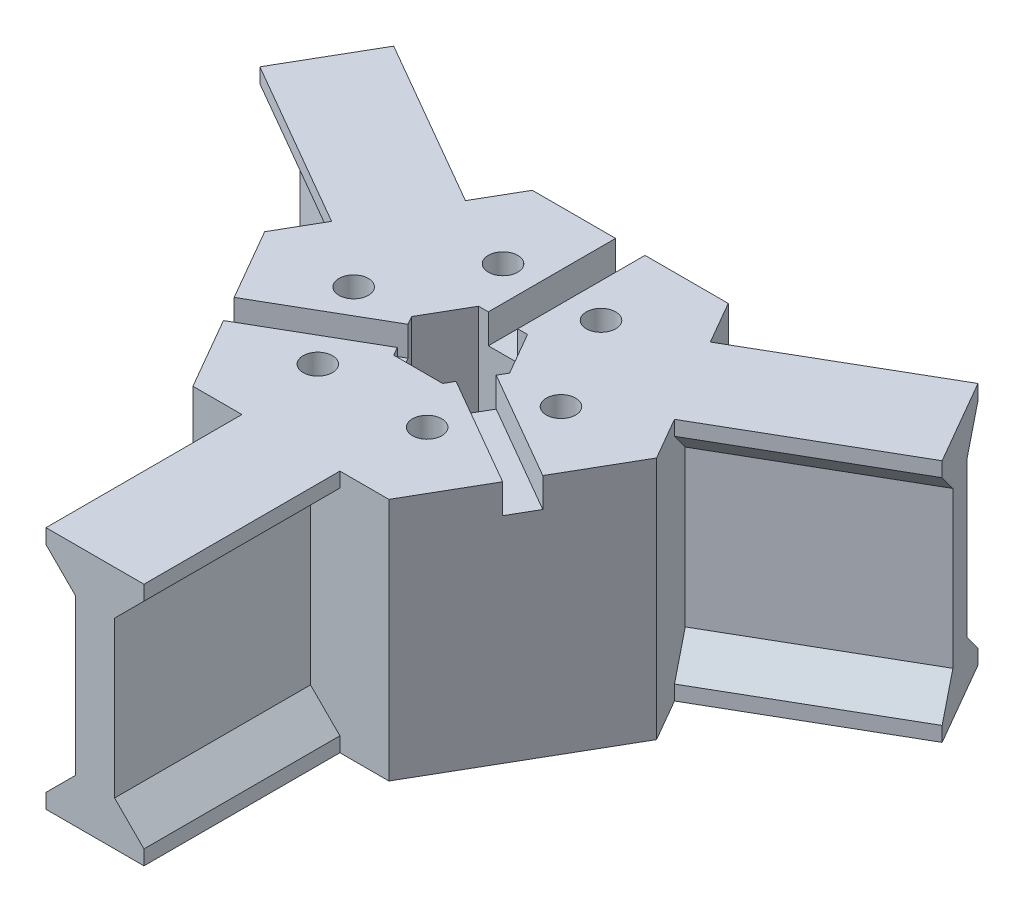
SolidWorks part; units mm, degrees
ref_plane "Front Plane" through (0, 0, 0) normal (0, 0, 1) x (1, 0, 0)
ref_plane "Top Plane" through (0, 0, 0) normal (0, 1, 0) x (1, 0, 0)
ref_plane "Right Plane" through (0, 0, 0) normal (1, 0, 0) x (0, 0, -1)
sketch "Sketch1" plane through (0, 0, 0) normal (0, 1, 0) x (1, 0, 0)
  line L0 (0, -27.9904) -> (0, -34.641) construction
  line L1 (20, 34.641) -> (-20, 34.641)
  line L2 (-20, 34.641) -> (-40, 0)
  line L3 (-40, 0) -> (-20, -34.641)
  line L4 (-20, -34.641) -> (20, -34.641)
  line L5 (20, -34.641) -> (40, 0)
  line L6 (40, 0) -> (20, 34.641)
  line L7 (5, 8.6603) -> (-5, 8.6603)
  line L8 (-5, 8.6603) -> (-10, 0)
  line L9 (-10, 0) -> (-5, -8.6603)
  line L10 (-5, -8.6603) -> (5, -8.6603)
  line L11 (5, -8.6603) -> (10, 0)
  line L12 (10, 0) -> (5, 8.6603)
  line L13 (-11.1603, -37.9904) -> (11.1603, -37.9904) construction
  line L14 (-11.1603, -37.9904) -> (-11.1603, -17.9904) construction
  line L16 (11.1603, -37.9904) -> (11.1603, -17.9904) construction
  line L17 (-11.1603, -37.9904) -> (11.1603, -17.9904) construction
  line L18 (-11.1603, -17.9904) -> (11.1603, -37.9904) construction
  line L19 (-5, -8.6603) -> (5, 8.6603) construction
  line L20 (-25.2452, 14.5753) -> (-30, 17.3205) construction
  line L21 (-21.1603, -0.6699) -> (-40.4904, 10.4904) construction
  line L23 (-10, 18.6603) -> (-29.3301, 29.8205) construction
  line L24 (-40.4904, 10.4904) -> (-29.3301, 29.8205) construction
  line L25 (-21.1603, -0.6699) -> (-29.3301, 29.8205) construction
  line L26 (-10, 18.6603) -> (-40.4904, 10.4904) construction
  line L27 (25.2452, 14.5753) -> (30, 17.3205) construction
  line L28 (21.1603, -0.6699) -> (40.4904, 10.4904) construction
  line L30 (10, 18.6603) -> (29.3301, 29.8205) construction
  line L31 (40.4904, 10.4904) -> (29.3301, 29.8205) construction
  line L32 (21.1603, -0.6699) -> (29.3301, 29.8205) construction
  line L33 (10, 18.6603) -> (40.4904, 10.4904) construction
  line L34 (0, -34.641) -> (0, -74.641) construction
  line L35 (-30, 17.3205) -> (-64.641, 37.3205) construction
  line L36 (30, 17.3205) -> (64.641, 37.3205) construction
  line L37 (-62.641, 40.7846) -> (-66.641, 33.8564)
  line L38 (4, -74.641) -> (-4, -74.641)
  line L39 (4, -74.641) -> (4, -34.641)
  line L40 (4, -34.641) -> (-4, -34.641)
  line L41 (-4, -74.641) -> (-4, -34.641)
  line L42 (4, -74.641) -> (-4, -34.641) construction
  line L43 (4, -34.641) -> (-4, -74.641) construction
  line L44 (62.641, 40.7846) -> (66.641, 33.8564)
  line L45 (66.641, 33.8564) -> (32, 13.8564)
  line L46 (62.641, 40.7846) -> (28, 20.7846)
  line L47 (-62.641, 40.7846) -> (-28, 20.7846)
  line L48 (-66.641, 33.8564) -> (-32, 13.8564)
  line L49 (-69.641, 28.6603) -> (-59.641, 45.9808)
  line L50 (59.641, 45.9808) -> (69.641, 28.6603)
  line L51 (-10, -74.641) -> (10, -74.641)
  line L52 (-69.641, 28.6603) -> (-35, 8.6603)
  line L53 (-59.641, 45.9808) -> (-25, 25.9808)
  line L54 (59.641, 45.9808) -> (25, 25.9808)
  line L55 (69.641, 28.6603) -> (35, 8.6603)
  line L56 (10, -74.641) -> (10, -34.641)
  line L57 (-10, -74.641) -> (-10, -34.641)
  line L58 (-21.1603, -0.6699) -> (-11.1603, -17.9904) construction
  line L59 (11.1603, -17.9904) -> (21.1603, -0.6699) construction
  line L60 (-10, 18.6603) -> (10, 18.6603) construction
  line L61 (0, 18.6603) -> (0, 8.6603) construction
  line L62 (-16.1603, -9.3301) -> (-7.5, -4.3301) construction
  line L63 (7.5, -4.3301) -> (16.1603, -9.3301) construction
  circle A0 centre (0, 0) radius 34.641 construction
  circle A1 centre (0, 0) radius 8.6603 construction
  circle A2 centre (-11.1603, -17.9904) radius 3
  circle A3 centre (11.1603, -17.9904) radius 3
  circle A4 centre (-11.1603, -37.9904) radius 2 construction
  circle A5 centre (11.1603, -37.9904) radius 2 construction
  circle A6 centre (-21.1603, -0.6699) radius 3
  circle A7 centre (-10, 18.6603) radius 3
  circle A8 centre (10, 18.6603) radius 3
  circle A9 centre (21.1603, -0.6699) radius 3
  point P20 (0, -27.9904)
  point P27 (-25.2452, 14.5753)
  point P36 (25.2452, 14.5753)
  point P45 (0, -54.641)
  point P56 (-64.641, 37.3205)
  point P59 (64.641, 37.3205)
  point P66 (-64.641, 37.3205)
  point P69 (64.641, 37.3205)
  point P72 (0, -74.641)
  dimension "D3" = 6
  dimension "D4" = 4
  dimension "D1" = 10
  dimension "D2" = 40
  dimension "D5" = 20
  dimension "D6" = 20
  dimension "D7" = 20
  dimension "D8" = 20
  dimension "D9" = 10
  dimension "D10" = 10
  dimension "D11" = 40
  dimension "D12" = 8
  dimension "D13" = 6
  dimension "D14" = 6
  dimension "D15" = 6
  dimension "D16" = 10
extrude "Boss-Extrude1" add sketch "Sketch1" along normal blind 49.8 contours L5 L6 L1 L2 L3 L4 A9 A8 A7 A6 A3 A2 L12 L11 L10 L9 L8 L7 | L53 L49 L47 L2 | L37 L48 L2 L47 | L49 L52 L2 L48 | L50 L54 L6 L46 | L44 L46 L6 L45 | L55 L50 L45 L6 | L51 L56 L4 L39 | L57 L51 L41 L4 | L41 L38 L39 L4 region at (21.5835, 0, -29.7817) region at (43.8205, 0, -33.3827) region at (-43.8205, 0, -33.3827) region at (47.3205, 0, -27.3205) region at (-47.3205, 0, -27.3205) region at (50.8205, 0, -21.2583) region at (-50.8205, 0, -21.2583) region at (7, 0, 54.641) region at (-7, 0, 54.641) region at (0, 0, 54.641)
sketch "Sketch2" plane through (0, 49.8, 0) normal (0, 1, 0) x (1, 0, 0)
  line L6 (-25.6699, -14.8205) -> (-7.5, -4.3301) construction
  line L8 (-10, 0) -> (-5, -8.6603) construction
  line L15 (25.6699, -14.8205) -> (7.5, -4.3301) construction
  line L27 (20, 34.641) -> (-20, 34.641) construction
  line L28 (-17.1132, 29.641) -> (-34.2265, 0)
  line L29 (-34.2265, 0) -> (-17.1132, -29.641)
  line L30 (-17.1132, -29.641) -> (17.1132, -29.641)
  line L31 (17.1132, -29.641) -> (34.2265, 0)
  line L32 (5, -8.6603) -> (10, 0) construction
  line L33 (34.2265, 0) -> (17.1132, 29.641)
  line L34 (17.1132, 29.641) -> (-17.1132, 29.641)
  line L35 (0, 8.6603) -> (0, 34.641) construction
  line L60 (5, 8.6603) -> (-5, 8.6603) construction
  line L61 (-15.1603, -4.134) -> (-15.1603, 2.7942)
  line L62 (-15.1603, 2.7942) -> (-21.1603, 6.2583)
  line L63 (-21.1603, 6.2583) -> (-27.1603, 2.7942)
  line L64 (-27.1603, 2.7942) -> (-27.1603, -4.134)
  line L65 (-27.1603, -4.134) -> (-21.1603, -7.5981)
  line L66 (-21.1603, -7.5981) -> (-15.1603, -4.134)
  line L67 (-4, 15.1962) -> (-4, 22.1244)
  line L68 (-4, 22.1244) -> (-10, 25.5885)
  line L69 (-10, 25.5885) -> (-16, 22.1244)
  line L70 (-16, 22.1244) -> (-16, 15.1962)
  line L71 (-16, 15.1962) -> (-10, 11.7321)
  line L72 (-10, 11.7321) -> (-4, 15.1962)
  line L73 (4, 15.1962) -> (10, 11.7321)
  line L74 (10, 11.7321) -> (16, 15.1962)
  line L75 (-3, 8.6603) -> (-3, 34.641)
  line L76 (6, -6.9282) -> (28.5, -19.9186)
  line L77 (16, 15.1962) -> (16, 22.1244)
  line L78 (16, 22.1244) -> (10, 25.5885)
  line L79 (10, 25.5885) -> (4, 22.1244)
  line L80 (4, 22.1244) -> (4, 15.1962)
  line L81 (15.1603, -4.134) -> (21.1603, -7.5981)
  line L82 (21.1603, -7.5981) -> (27.1603, -4.134)
  line L83 (-28.5, -19.9186) -> (-6, -6.9282)
  line L84 (27.1603, -4.134) -> (27.1603, 2.7942)
  line L85 (27.1603, 2.7942) -> (21.1603, 6.2583)
  line L86 (21.1603, 6.2583) -> (15.1603, 2.7942)
  line L87 (15.1603, 2.7942) -> (15.1603, -4.134)
  line L88 (17.1603, -21.4545) -> (17.1603, -14.5263)
  line L89 (17.1603, -14.5263) -> (11.1603, -11.0622)
  line L90 (11.1603, -11.0622) -> (5.1603, -14.5263)
  line L91 (5.1603, -14.5263) -> (5.1603, -21.4545)
  line L92 (5.1603, -21.4545) -> (11.1603, -24.9186)
  line L93 (11.1603, -24.9186) -> (17.1603, -21.4545)
  line L94 (-5.1603, -21.4545) -> (-5.1603, -14.5263)
  line L95 (-5.1603, -14.5263) -> (-11.1603, -11.0622)
  line L96 (-11.1603, -11.0622) -> (-17.1603, -14.5263)
  line L97 (-17.1603, -14.5263) -> (-17.1603, -21.4545)
  line L98 (-17.1603, -21.4545) -> (-11.1603, -24.9186)
  line L99 (-11.1603, -24.9186) -> (-5.1603, -21.4545)
  line L100 (-21.1603, 6.2583) -> (-28.25, 10.3516)
  line L101 (-16, 15.1962) -> (-23.0897, 19.2894)
  line L102 (-10, 25.5885) -> (-17.0897, 29.6817)
  line L103 (21.1603, 6.2583) -> (28.25, 10.3516)
  line L104 (10, 25.5885) -> (17.0897, 29.6817)
  line L105 (16, 15.1962) -> (23.0897, 19.2894)
  line L106 (27.1603, -4.134) -> (34.25, -0.0407)
  line L107 (17.1603, -21.4545) -> (17.1603, -29.641)
  line L108 (5.1603, -21.4545) -> (5.1603, -29.641)
  line L109 (-5.1603, -21.4545) -> (-5.1603, -29.641)
  line L110 (-17.1603, -21.4545) -> (-17.1603, -29.641)
  line L111 (-27.1603, -4.134) -> (-34.25, -0.0407)
  line L112 (-31.5, -14.7224) -> (-9, -1.7321)
  line L113 (9, -1.7321) -> (31.5, -14.7224)
  line L114 (3, 8.6603) -> (3, 34.641)
  line L115 (-40, 0) -> (-20, -34.641) construction
  line L116 (20, -34.641) -> (40, 0) construction
  line L117 (-31.5, -14.7224) -> (-28.5, -19.9186)
  line L118 (28.5, -19.9186) -> (31.5, -14.7224)
  line L119 (-3, 34.641) -> (3, 34.641)
  line L120 (-15.1603, -0.6699) -> (-13.4641, 0)
  line L121 (-8.1603, -12.7942) -> (-6.7321, -11.6603)
  line L122 (8.1603, -12.7942) -> (6.7321, -11.6603)
  line L123 (13.4641, 0) -> (15.1603, -0.6699)
  line L124 (6.7321, 11.6603) -> (7, 13.4641)
  line L125 (-6.7321, 11.6603) -> (-7, 13.4641)
  line L126 (-25.6699, 14.8205) -> (-10.0981, 5.8301) construction
  line L127 (6.7321, 11.6603) -> (-6.7321, 11.6603)
  line L128 (-6.7321, 11.6603) -> (-13.4641, 0)
  line L129 (-13.4641, 0) -> (-6.7321, -11.6603)
  line L130 (-6.7321, -11.6603) -> (6.7321, -11.6603)
  line L131 (6.7321, -11.6603) -> (13.4641, 0)
  line L132 (13.4641, 0) -> (6.7321, 11.6603)
  line L133 (10.0981, 5.8301) -> (25.6699, 14.8205) construction
  line L134 (0, -11.6603) -> (0, -29.641) construction
  circle A0 centre (0, 0) radius 29.641 construction
  circle A1 centre (-21.1603, -0.6699) radius 6 construction
  circle A2 centre (-10, 18.6603) radius 6 construction
  circle A3 centre (10, 18.6603) radius 6 construction
  circle A4 centre (0, 0) radius 11.6603 construction
  circle A5 centre (21.1603, -0.6699) radius 6 construction
  circle A6 centre (11.1603, -17.9904) radius 6 construction
  circle A7 centre (-11.1603, -17.9904) radius 6 construction
  circle A8 centre (-11.1603, -17.9904) radius 3 construction
  line M53 (10, 0) -> (5, -8.6603)
  line M55 (-5, -8.6603) -> (-10, 0)
  line M57 (-5, 8.6603) -> (5, 8.6603)
  line M58 (20, -34.641) -> (40, 0)
  line M64 (20, 34.641) -> (-20, 34.641)
  line M70 (-40, 0) -> (-20, -34.641)
  dimension "D1" = 5
  dimension "D2" = 6
  dimension "D3" = 3
  dimension "D4" = 3
  dimension "D5" = 3
  dimension "D6" = 3
extrude "Cut-Extrude1" [suppressed] cut sketch "Sketch2" against normal up to surface (49.8 mm away) contours L129 L112 L29 L83 | L131 L76 L31 L113 | L127 L114 L34 L75 | L128 L125 L72 L71 L101 L28 L100 L62 L61 L120 | L132 L123 L87 L86 L103 L33 L105 L74 L73 L124 | L130 L121 L95 L94 L109 L30 L108 L91 L90 L122
extrude "Cut-Extrude2" cut sketch "Sketch1<4>" along normal offset from surface (46.8 mm away) 3 contours L49 L52 L2 L48 | L53 L49 L47 L2 | A4 L57 L51 L41 L4 | A5 L56 L4 L39 L51 | L55 L50 L45 L6 | L50 L54 L6 L46 region at (43.8205, 0, -33.3827) region at (-43.8205, 0, -33.3827) region at (50.8205, 0, -21.2583) region at (-50.8205, 0, -21.2583) region at (7, 0, 54.641) region at (-7, 0, 54.641) up to face at (21.1603, 49.8, 3.6699)
sketch "Sketch1<4>" plane through (0, 0, 0) normal (0, 1, 0) x (1, 0, 0) same geometry as "Sketch1"
extrude "Boss-Extrude3" add sketch "Sketch1<5>" along normal offset from surface (3 mm away) 3 contours L57 L51 L41 L4 | L51 L56 L4 L39 | L49 L52 L2 L48 | L53 L49 L47 L2 | L55 L50 L45 L6 | L50 L54 L6 L46 region at (43.8205, 0, -33.3827) region at (-43.8205, 0, -33.3827) region at (50.8205, 0, -21.2583) region at (-50.8205, 0, -21.2583) region at (7, 0, 54.641) region at (-7, 0, 54.641) up to face at (21.1603, 0, 3.6699)
sketch "Sketch1<5>" plane through (0, 0, 0) normal (0, 1, 0) x (1, 0, 0) same geometry as "Sketch1"
chamfer "Chamfer1" distance 6 angle 45 12 edges at (-45.3205, 46.8, -30.7846) (-45.3205, 3, -30.7846) (-49.3205, 46.8, -23.8564) (-49.3205, 3, -23.8564) (49.3205, 46.8, -23.8564) (45.3205, 46.8, -30.7846) (45.3205, 3, -30.7846) (49.3205, 3, -23.8564) (-4, 3, 54.641) (4, 3, 54.641) (4, 46.8, 54.641) (-4, 46.8, 54.641)
extrude "Cut-Extrude3" cut sketch "Sketch2<3>" against normal offset from surface (6 mm away) 6 contours L112 L83 L29 M70 | L112 L129 L83 M55 | L76 L131 L113 M53 | L113 L31 L76 M58 | L131 L76 L31 L113 | L129 L112 L29 L83 | L127 L114 L34 L75 | L114 L127 L75 M57 | L34 L114 L75 M64 region at (0, 49.8, -32.141) region at (0, 49.8, -20.6506) region at (0, 49.8, -10.1603) region at (-17.884, 49.8, 10.3253) region at (-27.8349, 49.8, 16.0705) region at (-8.799, 49.8, 5.0801) region at (8.799, 49.8, 5.0801) region at (17.884, 49.8, 10.3253) region at (27.8349, 49.8, 16.0705) up to face at (21.1603, 49.8, 3.6699)
sketch "Sketch2<3>" plane through (0, 49.8, 0) normal (0, 1, 0) x (1, 0, 0) same geometry as "Sketch2"
